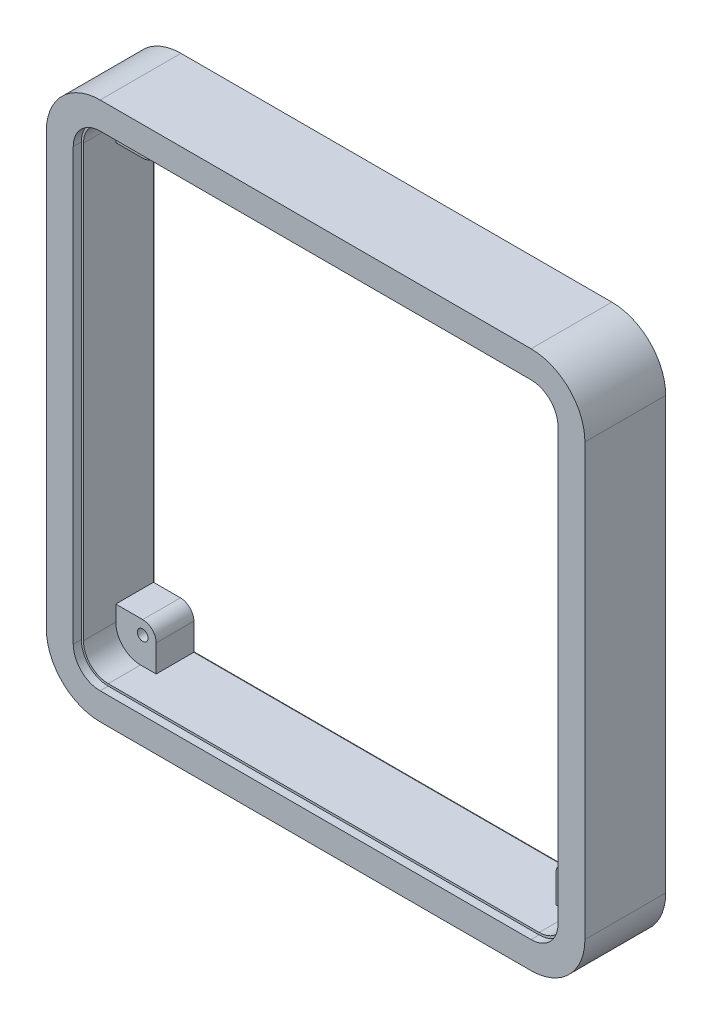
SolidWorks part; units mm, degrees
ref_plane "Piano frontale" through (0, 0, 0) normal (0, 0, 1) x (1, 0, 0)
ref_plane "Piano superiore" through (0, 0, 0) normal (0, 1, 0) x (1, 0, 0)
ref_plane "Piano destro" through (0, 0, 0) normal (1, 0, 0) x (0, 0, -1)
sketch "Sketch2" plane through (0, 0, 0) normal (0, 0, 1) x (1, 0, 0)
  line L5 (-100, -100) -> (100, -100)
  line L6 (-100, -100) -> (-100, 100)
  line L7 (-100, 100) -> (100, 100)
  line L8 (100, -100) -> (100, 100)
  line L9 (-100, -100) -> (100, 100) construction
  line L10 (-100, 100) -> (100, -100) construction
  point P0 (0, 0)
  dimension "D1" = 200
extrude "Boss-Extrude1" add sketch "Sketch2" along normal blind 30
fillet "Fillet1" radius 20 4 edges at (-100, -100, 15) (100, -100, 15) (100, 100, 15) (-100, 100, 15)
sketch "Sketch3" plane through (0, 0, 30) normal (0, 0, 1) x (1, 0, 0)
  line L8 (-90, 80) -> (-90, -80)
  line L9 (-80, -90) -> (80, -90)
  line L10 (90, -80) -> (90, 80)
  line L11 (80, 90) -> (-80, 90)
  line L12 (-90, 80) -> (-90, -80)
  line L13 (-80, -90) -> (80, -90)
  line L14 (90, -80) -> (90, 80)
  line L15 (80, 90) -> (-80, 90)
  arc A8 (-90, -80) -> (-80, -90) centre (-80, -80) ccw
  arc A9 (80, -90) -> (90, -80) centre (80, -80) ccw
  arc A10 (90, 80) -> (80, 90) centre (80, 80) ccw
  arc A11 (-80, 90) -> (-90, 80) centre (-80, 80) ccw
  arc A12 (-90, -80) -> (-80, -90) centre (-80, -80) ccw
  arc A13 (80, -90) -> (90, -80) centre (80, -80) ccw
  arc A14 (90, 80) -> (80, 90) centre (80, 80) ccw
  arc A15 (-80, 90) -> (-90, 80) centre (-80, 80) ccw
  dimension "D1" = 10
extrude "Cut-Extrude1" cut sketch "Sketch3" against normal blind 3
sketch "Sketch4" plane through (0, 0, 27) normal (0, 0, 1) x (1, 0, 0)
  line L16 (-89.2, 80) -> (-89.2, -80)
  line L17 (-80, -89.2) -> (80, -89.2)
  line L18 (89.2, -80) -> (89.2, 80)
  line L19 (80, 89.2) -> (-80, 89.2)
  line L20 (-89.2, 80) -> (-89.2, -80)
  line L21 (-80, -89.2) -> (80, -89.2)
  line L22 (89.2, -80) -> (89.2, 80)
  line L23 (80, 89.2) -> (-80, 89.2)
  arc A16 (-80, 89.2) -> (-89.2, 80) centre (-80, 80) ccw
  arc A17 (-89.2, -80) -> (-80, -89.2) centre (-80, -80) ccw
  arc A18 (80, -89.2) -> (89.2, -80) centre (80, -80) ccw
  arc A19 (89.2, 80) -> (80, 89.2) centre (80, 80) ccw
  arc A20 (-80, 89.2) -> (-89.2, 80) centre (-80, 80) ccw
  arc A21 (-89.2, -80) -> (-80, -89.2) centre (-80, -80) ccw
  arc A22 (80, -89.2) -> (89.2, -80) centre (80, -80) ccw
  arc A23 (89.2, 80) -> (80, 89.2) centre (80, 80) ccw
  dimension "D1" = 0.8
extrude "Cut-Extrude2" cut sketch "Sketch4" against normal through all
sketch "Sketch6" plane through (0, 0, 0) normal (0, 0, -1) x (-1, 0, 0)
  line L1 (-89.2, -74.2) -> (-74.2, -74.2)
  line L2 (-89.2, -74.2) -> (-89.2, -89.2)
  line L3 (-89.2, -89.2) -> (-74.2, -89.2)
  line L4 (-74.2, -74.2) -> (-74.2, -89.2)
  line L5 (-89.2, -80) -> (-89.2, 80) construction
  line L6 (80, -89.2) -> (-80, -89.2) construction
  line L18 (-74.2, 89.2) -> (-74.2, 74.2)
  line L19 (-89.2, 89.2) -> (89.2, 89.2) construction
  line L20 (-89.2, 89.2) -> (-89.2, -89.2) construction
  line L21 (-89.2, -89.2) -> (89.2, -89.2) construction
  line L22 (89.2, 89.2) -> (89.2, -89.2) construction
  line L23 (-89.2, 89.2) -> (89.2, -89.2) construction
  line L24 (-89.2, -89.2) -> (89.2, 89.2) construction
  line L25 (-74.2, 74.2) -> (-89.2, 74.2)
  line L26 (-89.2, 89.2) -> (-89.2, 74.2)
  line L27 (-74.2, 89.2) -> (-89.2, 89.2)
  line L28 (89.2, 74.2) -> (74.2, 74.2)
  line L29 (74.2, 74.2) -> (74.2, 89.2)
  line L30 (89.2, 89.2) -> (74.2, 89.2)
  line L31 (89.2, 74.2) -> (89.2, 89.2)
  line L32 (74.2, -89.2) -> (74.2, -74.2)
  line L33 (74.2, -74.2) -> (89.2, -74.2)
  line L34 (89.2, -89.2) -> (89.2, -74.2)
  line L35 (74.2, -89.2) -> (89.2, -89.2)
  point P4 (0, 0)
  point P14 (0, 0)
  point P19 (0, 0)
  point P24 (0, 0)
  point P29 (0, 0)
  dimension "D2" = 4
  dimension "D1" = 15
extrude "Boss-Extrude4" add sketch "Sketch6" against normal blind 15
fillet "Fillet2" radius 5 4 edges at (74.2, -74.2, 7.5) (-74.2, -74.2, 7.5) (-74.2, 74.2, 7.5) (74.2, 74.2, 7.5)
hole_wizard "Ø4.0 (4) Diameter Hole1" positions "Sketch8" profile "Sketch9" hole size "Ø4.0" standard "ANSI Metric" end condition through all
sketch "Sketch8" plane through (0, 0, 0) normal (0, 0, -1) x (-1, 0, 0)
  point P0 (-79.2, 79.2)
  point P3 (79.2, 79.2)
  point P6 (-79.2, -79.2)
  point P9 (79.2, -79.2)
sketch "Sketch9" plane through (79.2, 79.2, 0) normal (1, 0, 0) x (0, 1, 0)
  line L0 (0, 0) -> (0, 30)
  line L1 (0, 30) -> (2, 30)
  line L2 (2, 30) -> (2, 0)
  line L5 (2, 0) -> (0, 0)
  line L11 (0, -6.35) -> (0, 107.95) construction
  dimension "Thru Hole Dia." = 4
  dimension "Thru Hole Depth" = 30
sketch "Sketch10" plane through (0, 0, 0) normal (0, 0, -1) x (-1, 0, 0)
  line L4 (90, -80) -> (90, 80)
  line L5 (-80, -90) -> (80, -90)
  line L6 (-90, 80) -> (-90, -80)
  line L7 (80, 90) -> (-80, 90)
  line L8 (90, -80) -> (90, 80)
  line L9 (-80, -90) -> (80, -90)
  line L10 (-90, 80) -> (-90, -80)
  line L11 (80, 90) -> (-80, 90)
  arc A4 (90, 80) -> (80, 90) centre (80, 80) ccw
  arc A5 (80, -90) -> (90, -80) centre (80, -80) ccw
  arc A6 (-90, -80) -> (-80, -90) centre (-80, -80) ccw
  arc A7 (-80, 90) -> (-90, 80) centre (-80, 80) ccw
  arc A8 (90, 80) -> (80, 90) centre (80, 80) ccw
  arc A9 (80, -90) -> (90, -80) centre (80, -80) ccw
  arc A10 (-90, -80) -> (-80, -90) centre (-80, -80) ccw
  arc A11 (-80, 90) -> (-90, 80) centre (-80, 80) ccw
  dimension "D1" = 0
extrude "Cut-Extrude3" cut sketch "Sketch10" against normal blind 1
